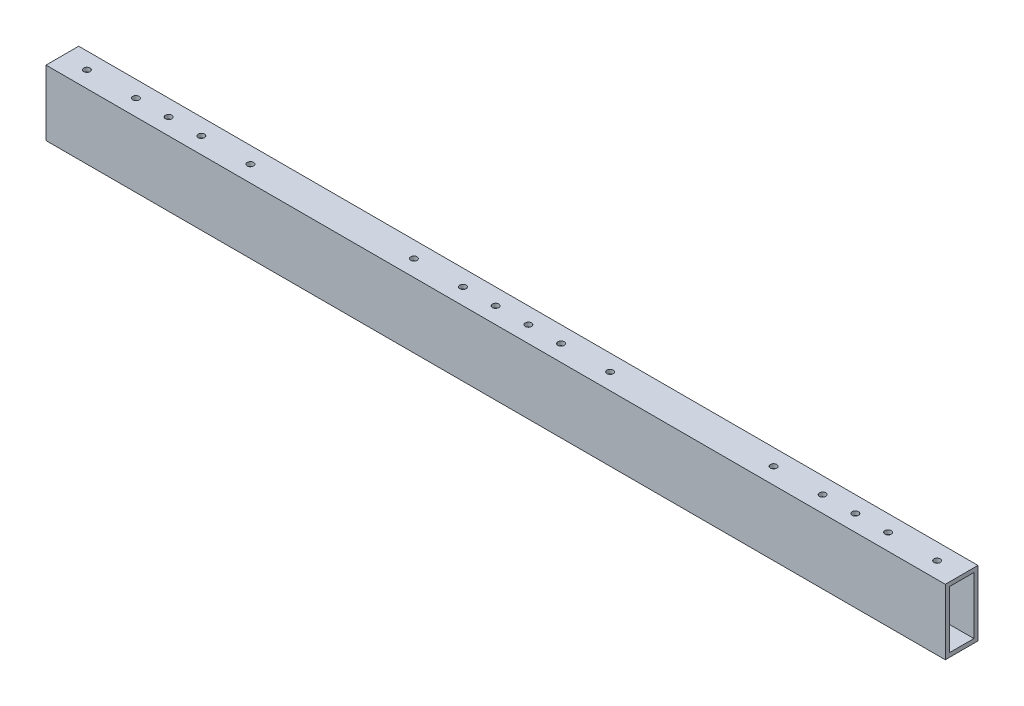
SolidWorks part; units mm, degrees
material "1060 Alloy"
ref_plane "Front Plane" through (0, 0, 0) normal (0, 0, 1) x (1, 0, 0)
ref_plane "Top Plane" through (0, 0, 0) normal (0, 1, 0) x (1, 0, 0)
ref_plane "Right Plane" through (0, 0, 0) normal (1, 0, 0) x (0, 0, -1)
sketch "Sketch1" plane through (0, 0, 0) normal (1, 0, 0) x (0, 0, -1)
  line L0 (3.175, -3.175) -> (3.175, 47.625)
  line L1 (0, 0) -> (-19.05, 0)
  line L2 (0, 0) -> (0, 44.45)
  line L3 (0, 44.45) -> (-19.05, 44.45)
  line L4 (-19.05, 0) -> (-19.05, 44.45)
  line L5 (3.175, 47.625) -> (-22.225, 47.625)
  line L6 (-22.225, -3.175) -> (-22.225, 47.625)
  line L7 (3.175, -3.175) -> (-22.225, -3.175)
  dimension "D2" = 50.8
  dimension "D3" = 25.4
  dimension "D1" = 3.175
extrude "Boss-Extrude1" add sketch "Sketch1" along normal blind 349.25 and the other way blind 349.25
sketch "Sketch6" plane through (0, 47.625, 0) normal (0, 1, 0) x (1, 0, 0)
  circle A0 centre (330.2, -9.525) radius 2.4638
  circle A1 centre (292.1, -9.525) radius 2.4638
  circle A2 centre (266.7, -9.525) radius 2.4638
  circle A3 centre (241.3, -9.525) radius 2.4638
  circle A4 centre (203.2, -9.525) radius 2.4638
  circle A5 centre (76.2, -9.525) radius 2.4638
  circle A6 centre (38.1, -9.525) radius 2.4638
  circle A7 centre (12.7, -9.525) radius 2.4638
  circle A8 centre (-12.7, -9.525) radius 2.4638
  circle A9 centre (-38.1, -9.525) radius 2.4638
  circle A10 centre (-76.2, -9.525) radius 2.4638
  circle A11 centre (-203.2, -9.525) radius 2.4638
  circle A12 centre (-241.3, -9.525) radius 2.4638
  circle A13 centre (-330.2, -9.525) radius 2.4638
  circle A14 centre (-292.1, -9.525) radius 2.4638
  circle A15 centre (-266.7, -9.525) radius 2.4638
extrude "Cut-Extrude1" cut sketch "Sketch6" against normal up to next
sketch "Sketch7" plane through (0, -3.175, 0) normal (0, -1, 0) x (-1, 0, 0)
  circle A0 centre (-266.7, -9.525) radius 2.4638
  circle A1 centre (-190.5, -9.525) radius 2.4638
  circle A2 centre (-114.3, -9.525) radius 2.4638
  circle A3 centre (-38.1, -9.525) radius 2.4638
  circle A4 centre (38.1, -9.525) radius 2.4638
  circle A5 centre (114.3, -9.525) radius 2.4638
  circle A6 centre (190.5, -9.525) radius 2.4638
  circle A7 centre (266.7, -9.525) radius 2.4638
extrude "Cut-Extrude2" cut sketch "Sketch7" against normal up to next
